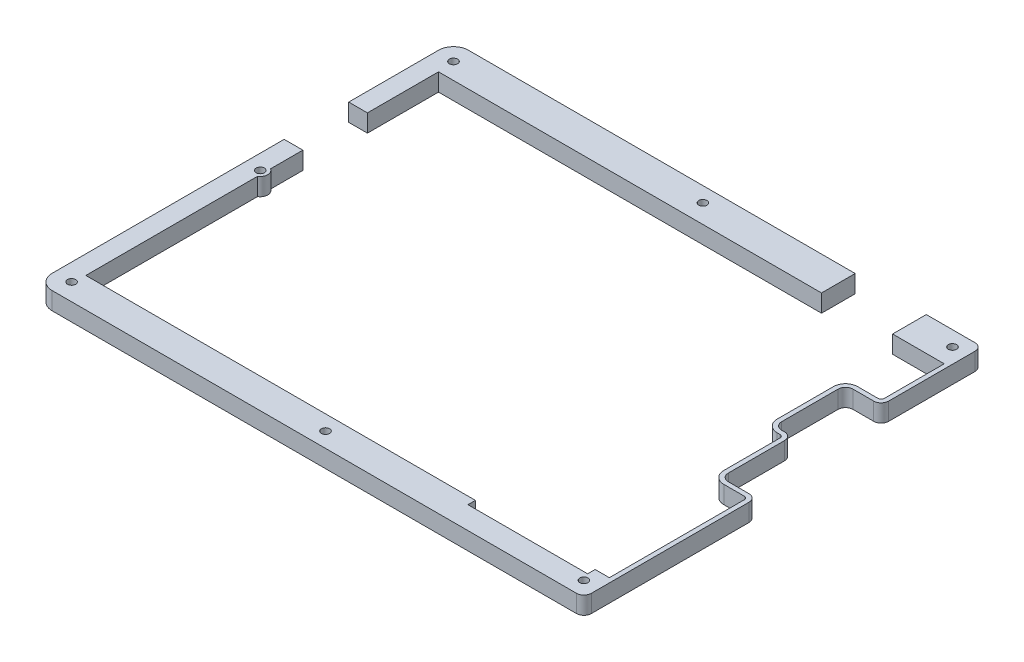
SolidWorks part; units mm, degrees
ref_plane "Front Plane" through (0, 0, 0) normal (0, 0, 1) x (1, 0, 0)
ref_plane "Top Plane" through (0, 0, 0) normal (0, 1, 0) x (1, 0, 0)
ref_plane "Right Plane" through (0, 0, 0) normal (1, 0, 0) x (0, 0, -1)
sketch "Sketch1" plane through (0, 0, 0) normal (0, 1, 0) x (1, 0, 0)
  line L3 (52.295, -42.625) -> (52.295, -51.625)
  line L5 (67.295, -49.625) -> (67.295, -26.575)
  line L10 (-70.055, 59.625) -> (70.055, 59.625)
  line L11 (65.295, -24.575) -> (59.765, -24.575)
  line L14 (57.765, -22.575) -> (57.765, -7.525)
  line L17 (59.765, -5.525) -> (60.525, -5.525)
  line L20 (62.525, -3.525) -> (62.525, 11.525)
  line L23 (64.525, 13.525) -> (70.045, 13.525)
  line L26 (72.045, 15.525) -> (72.055, 57.625)
  line L28 (66.0943, -26.575) -> (66.0943, -42.625)
  line L29 (65.295, -25.7757) -> (59.765, -25.7749)
  line L30 (-69.055, -6.375) -> (-69.055, 2.276)
  line L31 (56.5651, -22.575) -> (56.5651, -7.525)
  line L32 (59.765, -4.3251) -> (60.525, -4.3251)
  line L33 (-74.055, -23.625) -> (-69.055, -23.625)
  line L34 (-69.055, 5.734) -> (-69.055, 51.625)
  line L35 (-74.055, -6.375) -> (-69.055, -6.375)
  line L36 (35.0533, 51.625) -> (-69.055, 51.625)
  line L37 (35.0533, 51.625) -> (35.0533, 53.625)
  line L38 (35.0533, 53.625) -> (67.0538, 53.625)
  line L39 (67.0538, 53.625) -> (67.0538, 51.625)
  line L40 (70.8451, 51.625) -> (67.0538, 51.625)
  line L41 (-69.055, -23.625) -> (-69.055, -42.625)
  line L42 (61.3251, -3.525) -> (61.3251, 11.525)
  line L43 (64.525, 14.7249) -> (70.045, 14.7249)
  line L44 (70.8451, 15.525) -> (70.8451, 51.625)
  line L45 (52.295, -42.625) -> (66.0943, -42.625)
  line L46 (33.295, -42.625) -> (-69.055, -42.625)
  line L47 (33.295, -42.625) -> (33.295, -51.625)
  line L48 (-70.055, -51.625) -> (33.295, -51.625)
  line L49 (65.295, -51.625) -> (52.295, -51.625)
  line L50 (-74.055, -47.625) -> (-74.055, -23.625)
  line L51 (-74.055, -6.375) -> (-74.055, 55.625)
  arc A0 (-70.055, -51.625) -> (-74.055, -47.625) centre (-70.055, -47.625) cw
  arc A1 (-74.055, 55.625) -> (-70.055, 59.625) centre (-70.055, 55.625) cw
  arc A2 (65.295, -51.625) -> (67.295, -49.625) centre (65.295, -49.625) ccw
  arc A3 (67.295, -26.575) -> (65.295, -24.575) centre (65.295, -26.575) ccw
  arc A4 (59.765, -24.575) -> (57.765, -22.575) centre (59.765, -22.575) cw
  arc A5 (57.765, -7.525) -> (59.765, -5.525) centre (59.765, -7.525) cw
  arc A6 (60.525, -5.525) -> (62.525, -3.525) centre (60.525, -3.525) ccw
  arc A7 (62.525, 11.525) -> (64.525, 13.525) centre (64.525, 11.525) cw
  arc A8 (70.045, 13.525) -> (72.045, 15.525) centre (70.045, 15.525) ccw
  arc A9 (70.055, 59.625) -> (72.055, 57.625) centre (70.055, 57.625) cw
  circle A21 centre (-69.455, -47.025) radius 1.1
  circle A22 centre (63.295, -47.625) radius 1.1
  circle A23 centre (-3.405, -47.625) radius 1.1
  circle A24 centre (-69.455, 55.025) radius 1.1
  circle A25 centre (-1.0019, 55.625) radius 1.1
  circle A26 centre (68.0581, 55.625) radius 1.1
  circle A27 centre (-70.055, 4.005) radius 1.1
  arc A28 (66.0943, -26.575) -> (65.295, -25.7757) centre (65.295, -26.575) ccw
  arc A29 (56.5651, -22.575) -> (59.765, -25.7749) centre (59.765, -22.575) ccw
  arc A30 (56.5651, -7.525) -> (59.765, -4.3251) centre (59.765, -7.525) cw
  arc A31 (60.525, -4.3251) -> (61.3251, -3.525) centre (60.525, -3.525) ccw
  arc A32 (61.3251, 11.525) -> (64.525, 14.7249) centre (64.525, 11.525) cw
  arc A33 (70.045, 14.7249) -> (70.8451, 15.525) centre (70.045, 15.525) ccw
  arc A34 (-69.055, 5.734) -> (-69.055, 2.276) centre (-70.055, 4.005) cw
extrude "Boss-Extrude1" add sketch "Sketch1" along normal blind 4.7
move or copy body "Body-Move/Copy2" bodies to move or copy 102 101 copy no rotation origin (0, 2.35, -4) rotation axis (1, 0, 0) rotation angle 180
